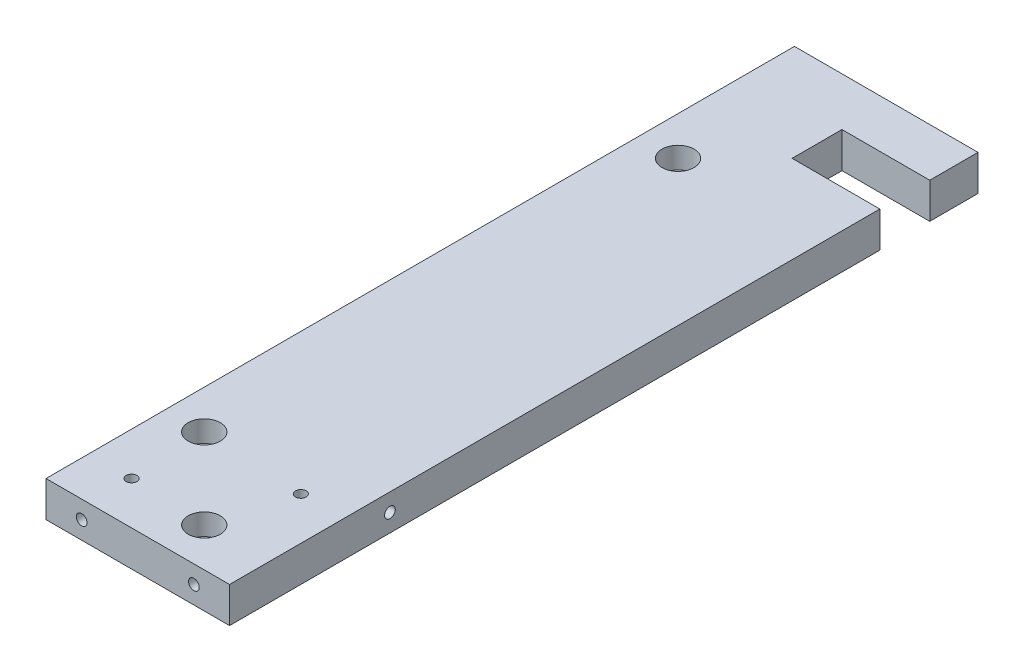
SolidWorks part; units mm, degrees
ref_plane "前视基准面" through (0, 0, 0) normal (0, 0, 1) x (1, 0, 0)
ref_plane "上视基准面" through (0, 0, 0) normal (0, 1, 0) x (1, 0, 0)
ref_plane "右视基准面" through (0, 0, 0) normal (1, 0, 0) x (0, 0, -1)
other "Configuration Table"
sketch "草图1" plane through (0, 0, 0) normal (0, 1, 0) x (1, 0, 0)
  line L1 (0, 0) -> (-25.75, 0)
  line L2 (0, 0) -> (0, 105)
  line L3 (0, 105) -> (-25.75, 105)
  line L4 (-25.75, 0) -> (-25.75, 105)
  line L6 (0, 98.2317) -> (-12.3137, 98.2317)
  line L7 (0, 98.2317) -> (0, 91.2317)
  line L8 (0, 91.2317) -> (-12.3137, 91.2317)
  line L9 (-12.3137, 98.2317) -> (-12.3137, 91.2317)
  circle A2 centre (-20.3137, 83.2317) radius 1.5
  circle A4 centre (-20.3137, 16.7637) radius 1.5
  circle A5 centre (-9, 5.45) radius 1.5
  circle A6 centre (-20.3137, 83.2317) radius 2.25
  circle A8 centre (-9, 5.45) radius 2.25
  circle A9 centre (-20.3137, 16.7637) radius 2.25
  point P2 (-9, 5.45)
  point P6 (0, 0)
  point P7 (-20.3137, 16.7637)
  dimension "D1" = 3
  dimension "D2" = 4.5
  dimension "D3" = 11.3137
  dimension "D4" = 11.3137
  dimension "D6" = 8
  dimension "D7" = 8
  dimension "D12" = 3
  dimension "D13" = 4.5
  dimension "D5" = 66.468
  dimension "D8" = 7
  dimension "D9" = 9
  dimension "D10" = 5.45
  dimension "D11" = 25.75
  dimension "D14" = 105
extrude "凸台-拉伸1" add sketch "草图1" along normal blind 5 contours L9 L6 L2 L3 L4 L1 L8 A9 A8 A6 | A6 | A9 | A8 region at (-13.0322, 0, -51.4056)
extrude "切除-拉伸1" cut sketch "草图1<12>" along normal through all contours A4 | A5 | A2
sketch "草图1<12>" plane through (0, 0, 0) normal (0, 1, 0) x (1, 0, 0) same geometry as "草图1"
extrude "切除-拉伸3" cut sketch "草图1<13>" against normal offset from surface (3 mm away) 2 from surface contours A6 | A9 | A8 up to face at (-20.3137, 0, -81.7317) starting at face at (-20.3137, 5, -81.7317)
sketch "草图1<13>" plane through (0, 0, 0) normal (0, 1, 0) x (1, 0, 0) same geometry as "草图1"
sketch "草图2" plane through (0, 0, 0) normal (0, 0, 1) x (1, 0, 0)
  line L0 (-25.75, 5) -> (-25.75, 0) construction
  line L1 (0, 5) -> (0, 0) construction
  circle A0 centre (-20.75, 2.5) radius 0.75
  circle A1 centre (-5, 2.5) radius 0.75
  point P4 (0, 0)
  point P9 (-25.75, 2.5)
  dimension "D3" = 1.5
  dimension "D4" = 15.75
  dimension "D1" = 5
  dimension "D2" = 5
extrude "切除-拉伸4" cut sketch "草图2" against normal blind 2 contours A0 | A1
sketch "草图3" plane through (0, 0, 0) normal (1, 0, 0) x (0, 0, -1)
  line L1 (0, 5) -> (0, 0) construction
  circle A0 centre (22.5, 2.5) radius 0.75
  point P2 (0, 0)
  point P5 (0, 2.5)
  dimension "D2" = 1.5
  dimension "D1" = 22.5
extrude "切除-拉伸5" cut sketch "草图3" against normal blind 2 contours A0
sketch "草图4" plane through (0, 5, 0) normal (0, 1, 0) x (1, 0, 0)
  line L2 (-25.75, 0) -> (-25.75, 105) construction
  line L3 (0, 0) -> (-25.75, 0) construction
  line L4 (0, 0) -> (0, 91.2317) construction
  circle A0 centre (-6, 16) radius 0.75
  circle A1 centre (-19.75, 6) radius 0.75
  point P5 (-20.3137, 16.7637)
  point P8 (-20.3137, 16.7637)
  point P10 (-20.1391, 16.7637)
  point P11 (0, 0)
  dimension "D1" = 1.5
  dimension "D2" = 6
  dimension "D3" = 6
  dimension "D4" = 6
  dimension "D5" = 10
extrude "切除-拉伸6" cut sketch "草图4" against normal through all contours A1 | A0
sketch "草图5" plane through (-25.75, 0, 0) normal (-1, 0, 0) x (0, 0, 1)
  line L0 (0, 5) -> (0, 0) construction
  circle A0 centre (-10, 2.5) radius 0.75
  circle A1 centre (-50, 2.5) radius 0.75
  circle A2 centre (-70, 2.5) radius 0.75
  circle A3 centre (-90, 2.5) radius 0.75
  circle A4 centre (-30, 2.5) radius 0.75
  point P8 (0, 0)
  point P12 (0, 2.5)
  dimension "D1" = 1.5
  dimension "D2" = 10
  dimension "D3" = 40
  dimension "D4" = 20
  dimension "D5" = 20
  dimension "D6" = 20
extrude "切除-拉伸7" cut sketch "草图5" against normal blind 2 contours A0 | A4 | A1 | A2 | A3
